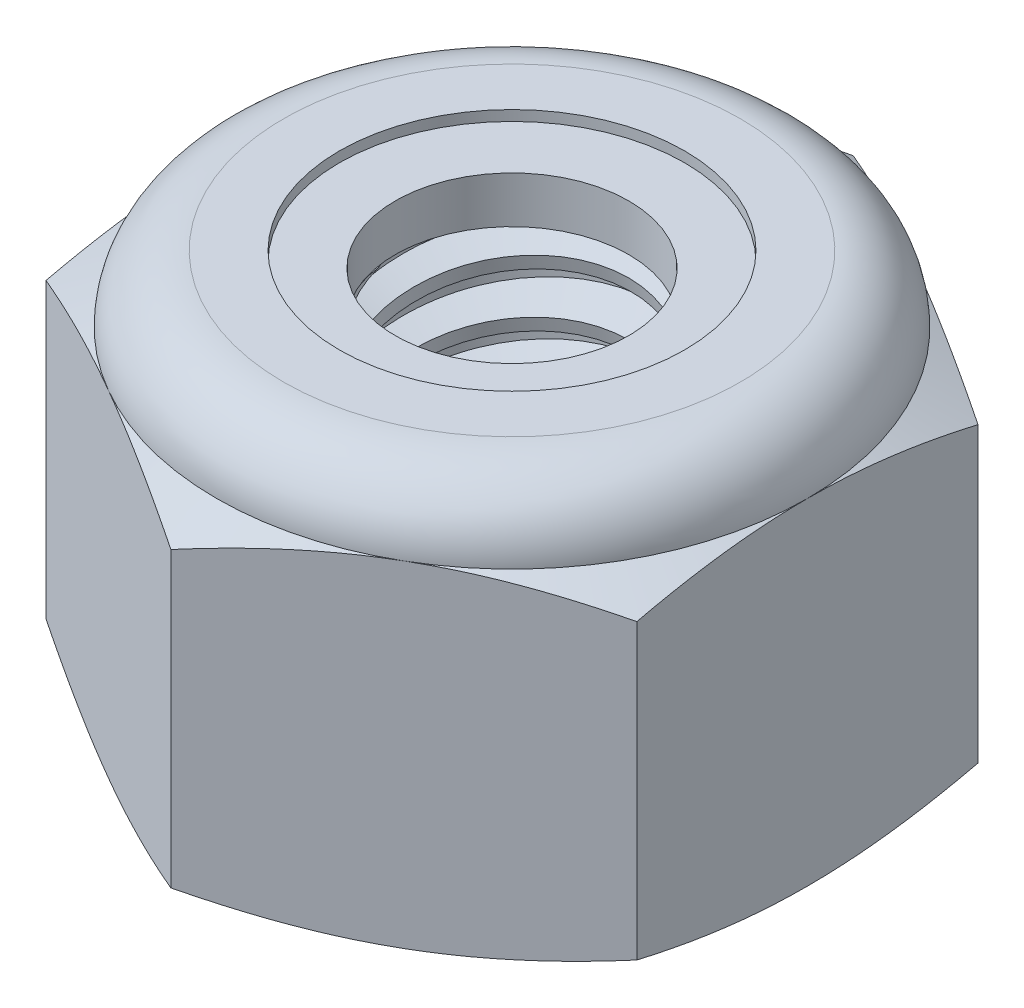
SolidWorks part; units mm, degrees
ref_plane "Front" through (0, 0, 0) normal (0, 0, 1) x (1, 0, 0)
ref_plane "Top" through (0, 0, 0) normal (0, 1, 0) x (1, 0, 0)
ref_plane "Right" through (0, 0, 0) normal (1, 0, 0) x (0, 0, -1)
sketch "Sketch1" plane through (0, 0, 0) normal (0, 1, 0) x (1, 0, 0)
  line L1 (0, 5.041) -> (-4.3656, 2.5205)
  line L2 (-4.3656, 2.5205) -> (-4.3656, -2.5205)
  line L3 (-4.3656, -2.5205) -> (0, -5.041)
  line L4 (0, -5.041) -> (4.3656, -2.5205)
  line L5 (4.3656, -2.5205) -> (4.3656, 2.5205)
  line L6 (4.3656, 2.5205) -> (0, 5.041)
  circle A0 centre (0, 0) radius 4.3656 construction
  dimension "Hex Flats" = 8.7312
extrude "Extrude1" add sketch "Sketch1" along normal blind 5.9531
sketch "Sketch2" plane through (0, 0, 0) normal (1, 0, 0) x (0, 0, -1)
  line L0 (-2.0828, 0) -> (-2.0828, 5.9531) construction
  line L1 (0, 0) -> (2.0828, 0)
  line L2 (0, 0) -> (0, 5.9531)
  line L3 (0, 5.9531) -> (2.0828, 5.9531)
  line L4 (2.0828, 0) -> (2.0828, 5.9531)
  line L5 (-2.5205, 5.9531) -> (2.5205, 5.9531) construction
  line L7 (0, -2.0828) -> (0, 0) construction
  dimension "Thread Dia" = 4.1656
revolve "Revolve1" add sketch "Sketch2" angle 360 about L7
sketch "Sketch3" plane through (0, 0, 0) normal (1, 0, 0) x (0, 0, -1)
  line L0 (2.0828, 5.9531) -> (-2.0828, 5.9531) construction
  line L1 (-2.0828, 5.9531) -> (-2.0828, 5.1594) construction
  line L2 (-2.0828, 5.1594) -> (2.0828, 5.9531) construction
  line L3 (2.0828, 5.9531) -> (2.1014, 5.8557) construction
  line L4 (2.1014, 5.8557) -> (2.2314, 5.1734)
  line L5 (2.2314, 5.1734) -> (1.7629, 5.3366)
  line L6 (1.7629, 5.3366) -> (1.7258, 5.5316)
  line L7 (1.7258, 5.5316) -> (2.1014, 5.8557)
  line L8 (1.7443, 5.4341) -> (2.1664, 5.5145) construction
  line L9 (2.0828, 5.9531) -> (2.0828, 5.4986) construction
  line L10 (2.0828, 5.4986) -> (-2.0828, 4.7049) construction
  line L11 (-2.0828, 4.7049) -> (-2.0828, 5.1594) construction
  line L12 (-0.1622, 5.9531) -> (0.1622, 4.2503) construction
  line L13 (-2.0828, 0) -> (-2.0828, 5.9531) construction
  line L14 (0, 5.9531) -> (2.0828, 5.9531) construction
  line L15 (2.0828, 0) -> (2.0828, 5.9531) construction
  point P13 (0, 5.1017)
  dimension "D1" = 0.0992
  dimension "D2" = 0.1984
  dimension "Thread Pitch" = 0.7937
  dimension "D4" = 60
  dimension "D5" = 0.7937
revolve "Cut-Revolve1" cut sketch "Sketch3" angle 360 about L12
pattern_linear "LPattern1" count 8 spacing 0.7937 along (0, -1, 0) count 2 spacing 0.7937 along (0, 1, 0) of "Cut-Revolve1"
sketch "Sketch4" plane through (0, 0, 0) normal (1, 0, 0) x (0, 0, -1)
  line L0 (0, 5.9531) -> (2.0828, 5.9531)
  line L1 (2.0828, 5.9531) -> (1.7258, 5.7866)
  line L2 (1.7258, 5.7866) -> (1.7258, 0.1665)
  line L3 (1.7258, 0.1665) -> (2.0828, 0)
  line L4 (2.0828, 0) -> (0, 0)
  line L5 (0, 0) -> (0, 5.9531)
  line L6 (2.0828, 0) -> (2.0828, 5.9531) construction
  line L7 (0, 5.9531) -> (2.0828, 5.9531) construction
  line L8 (0, 0) -> (2.0828, 0) construction
  line L9 (0, 0) -> (0, 5.9531) construction
  line L10 (0, 5.9531) -> (0, 6.3471) construction
  dimension "D1" = 25
revolve "Cut-Revolve2" cut sketch "Sketch4" angle 360 about L10
combine bodies "Combine1" operation type subtract main body 112 bodies to subtract 111
sketch "Sketch5" plane through (0, 0, 0) normal (1, 0, 0) x (0, 0, -1)
  line L0 (0, 0) -> (4.3656, 0)
  line L1 (4.3656, 0) -> (5.041, 0.3149)
  line L2 (5.041, 0.3149) -> (5.041, 4.646)
  line L3 (5.041, 4.646) -> (4.3656, 4.9609)
  line L4 (3.3734, 5.9531) -> (3.3734, 7.2231)
  line L5 (3.3734, 7.2231) -> (6.311, 7.2231)
  line L6 (6.311, 7.2231) -> (6.311, -1.27)
  line L7 (6.311, -1.27) -> (0, -1.27)
  line L8 (0, -1.27) -> (0, 0)
  line L9 (4.3656, 4.9609) -> (4.3656, 0) construction
  line L10 (0, 0) -> (2.0828, 0) construction
  line L13 (5.041, 2.4805) -> (6.311, 2.4805) construction
  line L14 (5.041, 5.9531) -> (5.041, 0) construction
  line L15 (0, 0) -> (0, 7.2231) construction
  line L20 (0, 7.2231) -> (3.3734, 7.2231) construction
  line L22 (0, 5.9531) -> (2.0828, 5.9531) construction
  arc A0 (4.3656, 4.9609) -> (3.3734, 5.9531) centre (3.3734, 4.9609) ccw
  dimension "D1" = 25
  dimension "D2" = 1.27
  dimension "D3" = 5.9531
  dimension "D4" = 0.9922
revolve "Cut-Revolve3" cut sketch "Sketch5" angle 360 about L15
sketch "Sketch6" plane through (0, 0, 0) normal (1, 0, 0) x (0, 0, -1)
  line L0 (0, 4.9609) -> (4.2132, 4.9609)
  line L1 (3.3734, 5.8007) -> (2.5496, 5.8007)
  line L2 (0, 7.2231) -> (0, 4.9609)
  line L3 (2.5496, 7.2231) -> (0, 7.2231)
  line L4 (0, 7.2231) -> (3.3734, 7.2231) construction
  line L5 (0, 0) -> (0, 7.2231) construction
  line L6 (0, 7.2231) -> (0, 44.323) construction
  line L7 (2.5496, 5.8007) -> (2.5496, 7.2231)
  line L8 (3.3734, 5.9531) -> (3.3734, 5.8007) construction
  line L9 (2.5496, 5.8007) -> (1.7258, 5.8007) construction
  line L10 (1.7258, 5.8007) -> (1.7258, 5.7866) construction
  arc A0 (4.2132, 4.9609) -> (3.3734, 5.8007) centre (3.3734, 4.9609) ccw
  arc A1 (4.3656, 4.9609) -> (3.3734, 5.9531) centre (3.3734, 4.9609) ccw construction
  dimension "D1" = 0.1524
revolve "Cut-Revolve4" cut sketch "Sketch6" angle 360 about L6
sketch "Sketch7" plane through (0, 0, 0) normal (1, 0, 0) x (0, 0, -1)
  line L0 (1.7258, 5.0371) -> (4.1332, 5.0371)
  line L1 (3.3734, 5.7245) -> (1.7258, 5.7245)
  line L2 (1.7258, 5.7245) -> (1.7258, 5.0371)
  line L3 (1.7258, 5.0371) -> (0, 5.0371) construction
  line L4 (0, 5.0371) -> (0, 5.7245) construction
  line L5 (0, 5.7245) -> (1.7258, 5.7245) construction
  line L6 (1.7258, 5.0371) -> (1.7258, 4.9609) construction
  line L7 (0, 4.9609) -> (4.2132, 4.9609) construction
  line L8 (3.3734, 5.7245) -> (3.3734, 5.8007) construction
  arc A0 (4.1332, 5.0371) -> (3.3734, 5.7245) centre (3.3734, 4.9609) ccw
  arc A2 (4.2132, 4.9609) -> (3.3734, 5.8007) centre (3.3734, 4.9609) ccw construction
  dimension "D1" = 0.0762
revolve "Revolve2" add sketch "Sketch7" angle 360 about L4
equation "\"D1@Sketch3\"=\"Thread Pitch@Sketch3\"/8"
equation "\"D2@Sketch3\"=\"Thread Pitch@Sketch3\"/4"
equation "\"D5@Sketch3\"=\"Thread Pitch@Sketch3\""
equation "\"D4@LPattern1\"=\"Thread Pitch@Sketch3\""
equation "\"D3@LPattern1\"=\"Thread Pitch@Sketch3\""
equation "\"D1@LPattern1\"=\"Height@Extrude1\"/\"Thread Pitch@Sketch3\""
equation "\"D4@Sketch5\"=\"Height@Extrude1\"/6"
